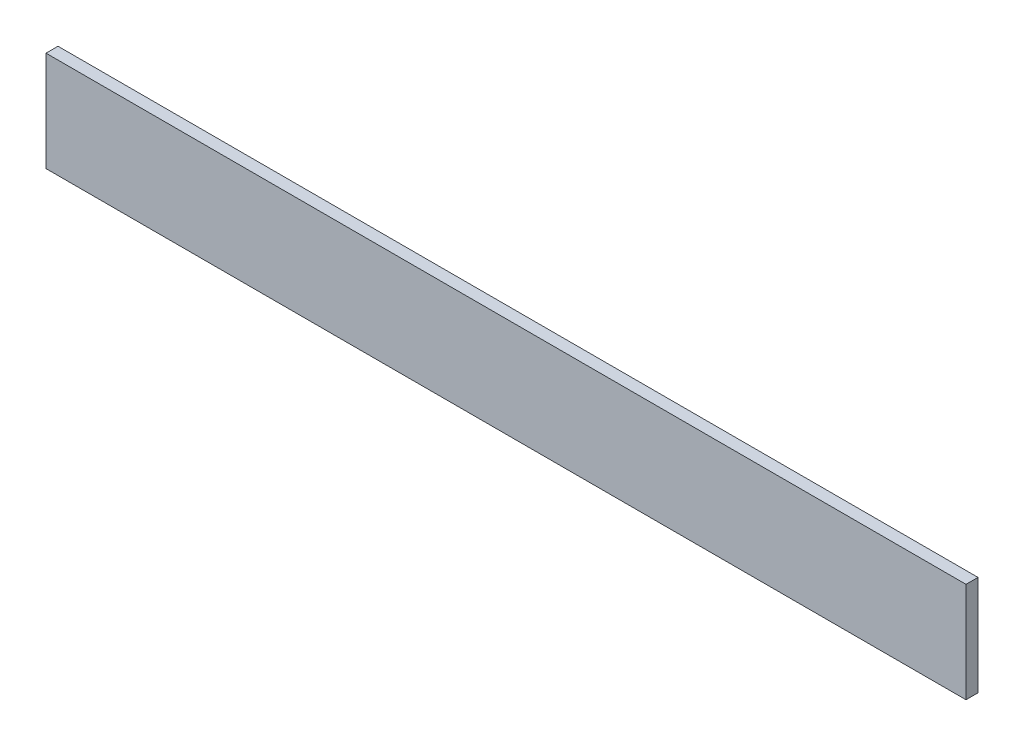
SolidWorks part; units mm, degrees
ref_plane "Front Plane" through (0, 0, 0) normal (0, 0, 1) x (1, 0, 0)
ref_plane "Top Plane" through (0, 0, 0) normal (0, 1, 0) x (1, 0, 0)
ref_plane "Right Plane" through (0, 0, 0) normal (1, 0, 0) x (0, 0, -1)
sketch "Sketch1" plane through (0, 0, 0) normal (0, 0, 1) x (1, 0, 0)
  line L1 (-115, -12.5) -> (115, -12.5)
  line L2 (-115, -12.5) -> (-115, 12.5)
  line L3 (-115, 12.5) -> (115, 12.5)
  line L4 (115, -12.5) -> (115, 12.5)
  line L5 (-115, -12.5) -> (115, 12.5) construction
  line L6 (-115, 12.5) -> (115, -12.5) construction
  point P0 (0, 0)
  dimension "D1" = 25
  dimension "D2" = 230
extrude "Boss-Extrude1" add sketch "Sketch1" along normal blind 3
equation "\"PCLength\"= 320mm'Length across I/O from PS to GPU"
equation "\"PCWidth\"= 242mm'Distance of longest part parallel to GPU(ussually GPU)"
equation "\"PCHeight\"= 172mm'Tallest point with mobo laying flat"
equation "\"WallThickness\"= 9mm'Thickness of each outer tank wall"
equation "\"ThermoBarrierThickness\"= 3mm'Thickness of barrier between hot side and cold side"
equation "\"HotSideGap\"= 25mm'Space in the hot side for a pump"
equation "\"PCClearance\"= 30mm'Clearance from top of tank to top of PC"
equation "\"RadiatorHeight\"= 275mm'Final Height from ground of radiators"
equation "\"AirflowGap\"= 36mm'Distance between radiators and tank for airflow"
equation "\"VolumeSubtraction\"= 230mm"
equation "\"D1@Sketch1\"=\"HotSideGap\""
equation "\"D2@Sketch1\"=\"VolumeSubtraction\""
equation "\"D1@Boss-Extrude1\"=\"ThermoBarrierThickness\""
